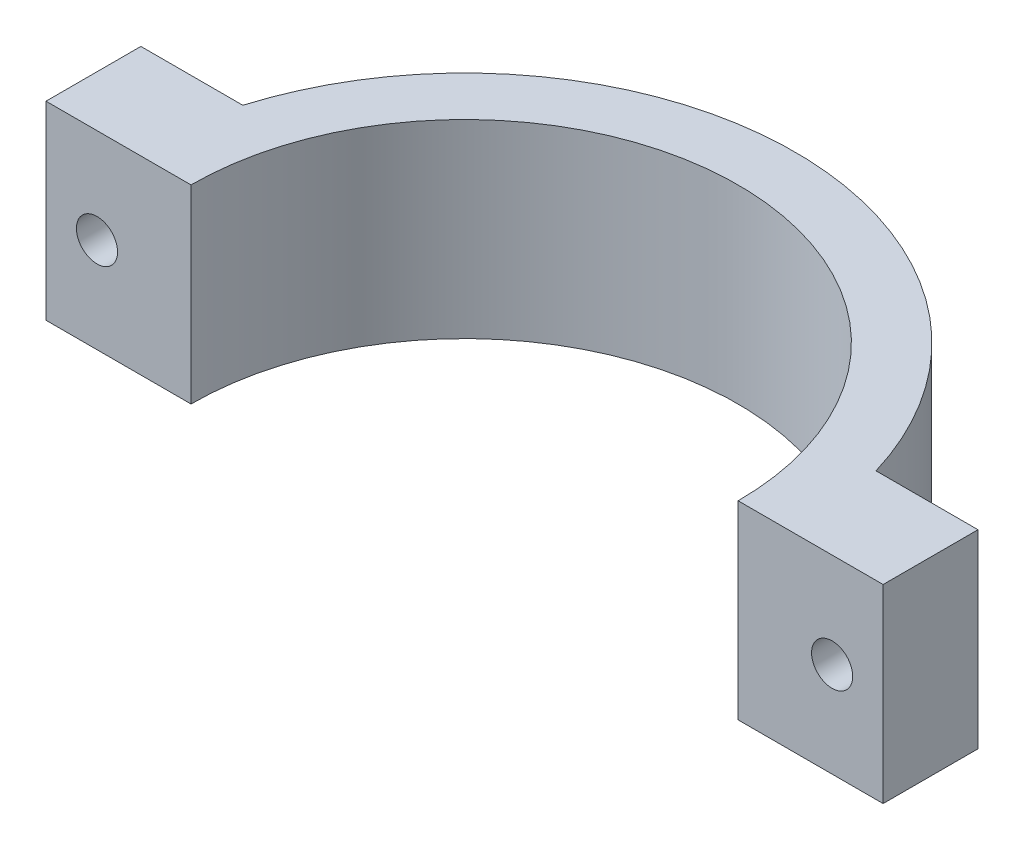
SolidWorks part; units mm, degrees
ref_plane "Front Plane" through (0, 0, 0) normal (0, 0, 1) x (1, 0, 0)
ref_plane "Top Plane" through (0, 0, 0) normal (0, 1, 0) x (1, 0, 0)
ref_plane "Right Plane" through (0, 0, 0) normal (1, 0, 0) x (0, 0, -1)
sketch "Sketch1" plane through (0, 0, 0) normal (0, 1, 0) x (1, 0, 0)
  line L3 (0, 0) -> (0, 43.25) construction
  line L14 (-66.175, 0) -> (-66.175, 15)
  line L16 (43.25, 0) -> (66.175, 0)
  line L17 (66.175, 0) -> (66.175, 15)
  line L18 (-66.175, 0) -> (-43.25, 0)
  line L19 (-66.175, 15) -> (-50.0506, 15)
  line L20 (50.0506, 15) -> (66.175, 15)
  circle A0 centre (0, 0) radius 43.25 construction
  arc A1 (-43.25, 0) -> (43.25, 0) centre (0, 0) cw
  arc A2 (-50.0506, 15) -> (50.0506, 15) centre (0, 0) cw
  dimension "D1" = 86.5
  dimension "D2" = 52.25
  dimension "D3" = 15
  dimension "D4" = 132.35
extrude "Boss-Extrude1" add sketch "Sketch1" along normal mid plane 30
sketch "Sketch2" plane through (0, 0, -15) normal (0, 0, -1) x (-1, 0, 0)
  line L0 (58.1128, -15) -> (58.1128, 15) construction
  line L1 (50.0506, -15) -> (66.175, -15) construction
  line L2 (50.0506, 15) -> (66.175, 15) construction
  line L3 (0, 0) -> (0, 15) construction
  line L4 (50.0506, 15) -> (-50.0506, 15) construction
  circle A1 centre (58.1128, 0) radius 3.25
  circle A2 centre (-58.1128, 0) radius 3.25
  dimension "D1" = 6.5
extrude "Cut-Extrude1" cut sketch "Sketch2" against normal through all
